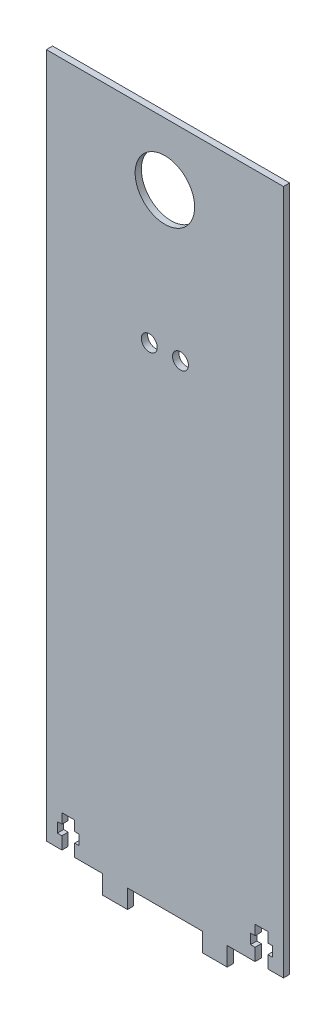
SolidWorks part; units mm, degrees
ref_plane "前视基准面" through (0, 0, 0) normal (0, 0, 1) x (1, 0, 0)
ref_plane "上视基准面" through (0, 0, 0) normal (0, 1, 0) x (1, 0, 0)
ref_plane "右视基准面" through (0, 0, 0) normal (1, 0, 0) x (0, 0, -1)
sketch "草图1" plane through (0, 0, 0) normal (0, 0, 1) x (1, 0, 0)
  line L0 (-30.7912, 3.1303) -> (31.2088, 3.1303) construction
  line L1 (-30.7912, 3.1303) -> (-30.7912, 5.1553) construction
  line L2 (-28.7412, 3.1303) -> (-28.7412, 7.1303)
  line L3 (-28.7412, 7.1303) -> (-27.2912, 7.1303)
  line L4 (-27.2912, 7.1303) -> (-27.2912, 10.3303)
  line L5 (-27.2912, 10.3303) -> (-28.7412, 10.3303)
  line L6 (-28.7412, 10.3303) -> (-28.7412, 13.5303)
  line L7 (-28.7412, 13.5303) -> (-32.8412, 13.5303)
  line L8 (-34.2912, 7.1303) -> (-34.2912, 10.3303)
  line L9 (-32.8412, 10.3303) -> (-32.8412, 13.5303)
  line L10 (-32.8412, 3.1303) -> (-32.8412, 7.1303)
  line L11 (-32.8412, 7.1303) -> (-34.2912, 7.1303)
  line L12 (-34.2912, 10.3303) -> (-32.8412, 10.3303)
  line L13 (-32.8412, 3.1303) -> (-37.8412, 3.1303)
  line L14 (-37.8412, 3.1303) -> (-37.8412, 223.1303)
  line L15 (-19.7912, 3.1303) -> (-19.7912, -2.8697)
  line L16 (-19.7912, -2.8697) -> (-11.7912, -2.8697)
  line L17 (-11.7912, -2.8697) -> (-11.7912, 3.1303)
  line L18 (-15.7912, -2.8697) -> (-15.7912, 3.1303) construction
  line L19 (-28.7412, 3.1303) -> (-19.7912, 3.1303)
  line L20 (0.2088, 3.1303) -> (0.2088, -7.8241) construction
  line L21 (-11.7912, 3.1303) -> (12.2088, 3.1303)
  line L22 (16.2088, -2.8697) -> (16.2088, 3.1303) construction
  line L23 (31.2088, 3.1303) -> (31.2088, 5.1553) construction
  line L24 (29.1588, 3.1303) -> (20.2088, 3.1303)
  line L25 (12.2088, -2.8697) -> (12.2088, 3.1303)
  line L26 (20.2088, -2.8697) -> (12.2088, -2.8697)
  line L27 (20.2088, 3.1303) -> (20.2088, -2.8697)
  line L28 (38.2588, 3.1303) -> (38.2588, 223.1303)
  line L29 (33.2588, 3.1303) -> (38.2588, 3.1303)
  line L30 (34.7088, 10.3303) -> (33.2588, 10.3303)
  line L31 (33.2588, 7.1303) -> (34.7088, 7.1303)
  line L32 (33.2588, 3.1303) -> (33.2588, 7.1303)
  line L33 (33.2588, 10.3303) -> (33.2588, 13.5303)
  line L34 (34.7088, 7.1303) -> (34.7088, 10.3303)
  line L35 (29.1588, 13.5303) -> (33.2588, 13.5303)
  line L36 (29.1588, 10.3303) -> (29.1588, 13.5303)
  line L37 (27.7088, 10.3303) -> (29.1588, 10.3303)
  line L38 (27.7088, 7.1303) -> (27.7088, 10.3303)
  line L39 (29.1588, 7.1303) -> (27.7088, 7.1303)
  line L40 (29.1588, 3.1303) -> (29.1588, 7.1303)
  line L41 (-37.8412, 223.1303) -> (38.2588, 223.1303)
  line L42 (0.2088, 3.1303) -> (0.2088, 203.1303) construction
  circle A0 centre (0.2088, 203.1303) radius 9.55
  circle A1 centre (0.2088, 203.1303) radius 40 construction
  circle A2 centre (-4.7912, 158.1303) radius 2.55
  circle A3 centre (5.2088, 158.1303) radius 2.55
  point P16 (-30.7912, 13.5303)
  point P47 (31.2088, 13.5303)
  dimension "D10" = 19.1
  dimension "D13" = 80
  dimension "D14" = 5.1
  dimension "D1" = 62
  dimension "D2" = 2.05
  dimension "D3" = 3.2
  dimension "D4" = 4
  dimension "D5" = 3.5
  dimension "D6" = 8
  dimension "D7" = 6
  dimension "D8" = 15
  dimension "D9" = 5
  dimension "D11" = 200
  dimension "D12" = 20
  dimension "D15" = 45
  dimension "D16" = 5
extrude "凸台-拉伸1" add sketch "草图1" along normal blind 2
sketch "草图2" plane through (0, 3.1303, 0) normal (0, -1, 0) x (1, 0, 0)
  line L0 (29.1588, 1) -> (33.2588, 1) construction
  line L1 (29.1588, 2) -> (29.1588, 0) construction
  line L2 (33.2588, 2) -> (33.2588, 0) construction
  circle A0 centre (31.2088, 1) radius 2.05
